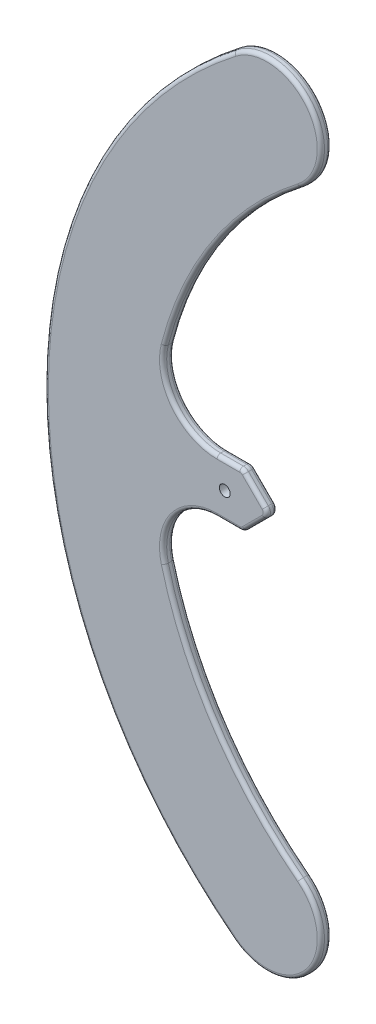
SolidWorks part; units mm, degrees
ref_plane "Front Plane" through (0, 0, 0) normal (0, 0, 1) x (1, 0, 0)
ref_plane "Top Plane" through (0, 0, 0) normal (0, 1, 0) x (1, 0, 0)
ref_plane "Right Plane" through (0, 0, 0) normal (1, 0, 0) x (0, 0, -1)
sketch "Sketch1" plane through (0, 0, 0) normal (0, 0, 1) x (1, 0, 0)
  line L0 (-32.8019, 0) -> (18.2589, 0) construction
  line L1 (70.5, 105) -> (70.5, 135) construction
  line L2 (205.5, -110) -> (-64.5, -110)
  line L3 (205.5, -110) -> (205.5, 110)
  line L4 (205.5, 110) -> (-64.5, 110)
  line L5 (-19.5, 6.5) -> (-19.5, -6.5)
  line L6 (-18.5, -7.5) -> (-9.5, -7.5)
  line L7 (-9.5, -7.5) -> (-2, 0)
  line L9 (-9.5, 7.5) -> (-18.5, 7.5)
  line L11 (-18.5, -7.5) -> (-9.5, -7.5)
  line L15 (-64.5, -110) -> (-64.5, 110)
  line L16 (205.5, -110) -> (-64.5, 110) construction
  line L17 (205.5, 110) -> (-64.5, -110) construction
  line L18 (-18, 7.5) -> (-34.2318, 7.5)
  line L19 (-18.5, -7.5) -> (-34.2318, -7.5)
  line L146 (-9.5, 7.5) -> (-18.5, 7.5)
  line L162 (-9.5, -7.5) -> (-2, 0)
  line L169 (-2, 0) -> (-9.5, 7.5)
  line L170 (-2, 0) -> (-9.5, 7.5)
  line L176 (-19.5, 6.5) -> (-19.5, -6.5)
  circle A0 centre (-14.5, 0) radius 1.5 construction
  arc A2 (-19.5, -6.5) -> (-18.5, -7.5) centre (-18.5, -6.5) ccw
  circle A6 centre (-14.5, 0) radius 1.5
  circle A7 centre (-14.5, 0) radius 1.5
  circle A8 centre (70.5, 0) radius 135
  circle A9 centre (70.5, 0) radius 105
  circle A11 centre (-2.8144, 95) radius 15
  circle A12 centre (-2.8144, -95) radius 15
  arc A65 (-19.5, -6.5) -> (-18.5, -7.5) centre (-18.5, -6.5) ccw
  arc A77 (-18.5, 7.5) -> (-19.5, 6.5) centre (-18.5, 6.5) ccw
  arc A78 (-18.5, 7.5) -> (-19.5, 6.5) centre (-18.5, 6.5) ccw
  point P19 (-64.5, 0)
  point P27 (70.5, 110)
  dimension "D3" = 270
  dimension "D5" = 30
  dimension "D2" = 55
  dimension "D4" = 220
  dimension "D1" = 0
extrude "Boss-Extrude1" add sketch "Sketch1" along normal blind 2.9 contours A11 | A8 A12 A9 A11 | A12 | L18 A9 L19 | L146 L11 L162 L170 A6 region at (-2.8144, -95, 0) region at (-37.1858, 0, 0) region at (-2.8144, 95, 0) region at (-26.9408, 0, 0) region at (-12.3671, 0, 0)
fillet "Fillet1" radius 15 2 edges at (-34.2318, -7.5, 1.45) (-34.2318, 7.5, 1.45)
fillet "Fillet2" radius 2 3 edges at (-9.5, -7.5, 1.45) (-9.5, 7.5, 1.45) (-2, 0, 1.45)
fillet "Fillet3" radius 1 28 edges at (-13.4853, 7.5, 2.9) (-9.5631, 7.3478, 2.9) (-6.1642, 4.1642, 2.9) (-2.8284, 0, 2.9) (-6.1642, -4.1642, 2.9) (-9.5631, -7.3478, 2.9) (-13.4853, -7.5, 2.9) (-28.5007, -13.3144, 2.9) (-17.1494, -57.815, 2.9) (9.0606, -104.1643, 2.9) (-64.5, 0, 2.9) (9.0606, 104.1643, 2.9) (-17.1494, 57.815, 2.9) (-17.1494, 57.815, 0) (9.0606, 104.1643, 0) (-64.5, 0, 0) (9.0606, -104.1643, 0) (-17.1494, -57.815, 0) (-28.5007, -13.3144, 0) (-13.4853, -7.5, 0) (-9.5631, -7.3478, 0) (-6.1642, -4.1642, 0) (-2.8284, 0, 0) (-6.1642, 4.1642, 0) (-9.5631, 7.3478, 0) (-13.4853, 7.5, 0) (-28.5007, 13.3144, 2.9) (-28.5007, 13.3144, 0)
